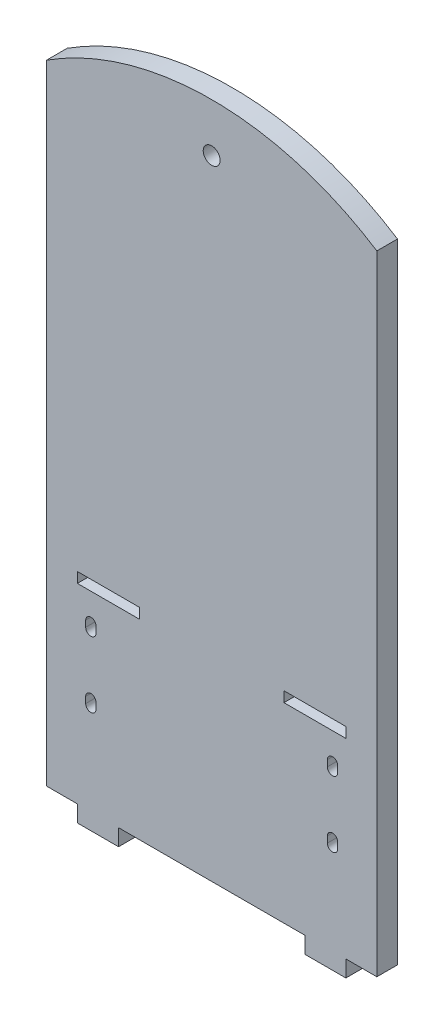
SolidWorks part; units mm, degrees
ref_plane "前基準面" through (0, 0, 0) normal (0, 0, 1) x (1, 0, 0)
ref_plane "上基準面" through (0, 0, 0) normal (0, 1, 0) x (1, 0, 0)
ref_plane "右基準面" through (0, 0, 0) normal (1, 0, 0) x (0, 0, -1)
sketch "草圖1" plane through (0, 0, 0) normal (0, 0, 1) x (1, 0, 0)
  line L0 (-80, 0) -> (-65, 0)
  line L1 (-80, 0) -> (-80, 304.5)
  line L2 (80, 0) -> (80, 304.5)
  line L3 (0, 299.9843) -> (0, -20.7711) construction
  line L5 (-65, 0) -> (-65, -8)
  line L6 (-65, -8) -> (-45.1, -8)
  line L7 (-45.1, 0) -> (-45.1, -8)
  line L12 (65, -8) -> (45.1, -8)
  line L13 (45.1, 0) -> (45.1, -8)
  line L15 (65, 0) -> (65, -8)
  line L16 (-45.1, 0) -> (45.1, 0)
  line L17 (65, 0) -> (80, 0)
  line L18 (-21.8, 304.5) -> (-15, 33.5) construction
  line L19 (28.5, 5) -> (-28.5, 5) construction
  line L20 (28.5, 5) -> (28.5, 62) construction
  line L21 (28.5, 62) -> (-28.5, 62) construction
  line L22 (-28.5, 5) -> (-28.5, 62) construction
  line L23 (21.8, 304.5) -> (15, 33.5) construction
  line L24 (-58.525, 76.1) -> (-58.525, 79.1) construction
  line L25 (-61.025, 76.1) -> (-61.025, 79.1)
  line L26 (-56.025, 76.1) -> (-56.025, 79.1)
  line L27 (-58.525, 44.1) -> (-58.525, 47.1) construction
  line L28 (-61.025, 44.1) -> (-61.025, 47.1)
  line L29 (-56.025, 44.1) -> (-56.025, 47.1)
  line L30 (-67.625, 89.2) -> (-67.625, 34) construction
  line L31 (-67.625, 89.2) -> (-49.425, 89.2) construction
  line L32 (-49.425, 89.2) -> (-49.425, 34) construction
  line L33 (-67.625, 34) -> (-49.425, 34) construction
  line L34 (-49.425, 61.6) -> (-67.625, 61.6) construction
  line L35 (-58.525, 89.2) -> (-58.525, 34) construction
  line L36 (58.525, 44.1) -> (58.525, 47.1) construction
  line L37 (61.025, 44.1) -> (61.025, 47.1)
  line L38 (56.025, 44.1) -> (56.025, 47.1)
  line L39 (58.525, 76.1) -> (58.525, 79.1) construction
  line L40 (61.025, 76.1) -> (61.025, 79.1)
  line L41 (56.025, 76.1) -> (56.025, 79.1)
  line L42 (76.4706, 328) -> (-76.4706, 328) construction
  arc A0 (-80, 304.5) -> (80, 304.5) centre (0, 304.5) cw construction
  circle A1 centre (0, 304.5) radius 4.1
  circle A2 centre (0, 33.5) radius 4 construction
  circle A3 centre (0, 33.5) radius 15 construction
  circle A4 centre (0, 304.5) radius 21.8 construction
  arc A5 (-61.025, 76.1) -> (-56.025, 76.1) centre (-58.525, 76.1) ccw
  arc A6 (-56.025, 79.1) -> (-61.025, 79.1) centre (-58.525, 79.1) ccw
  arc A7 (-61.025, 44.1) -> (-56.025, 44.1) centre (-58.525, 44.1) ccw
  arc A8 (-56.025, 47.1) -> (-61.025, 47.1) centre (-58.525, 47.1) ccw
  arc A9 (61.025, 44.1) -> (56.025, 44.1) centre (58.525, 44.1) cw
  arc A10 (56.025, 47.1) -> (61.025, 47.1) centre (58.525, 47.1) cw
  arc A11 (61.025, 76.1) -> (56.025, 76.1) centre (58.525, 76.1) cw
  arc A12 (56.025, 79.1) -> (61.025, 79.1) centre (58.525, 79.1) cw
  arc A13 (-80, 304.5) -> (80, 304.5) centre (0, 180.0798) cw
  point P17 (0, 62)
  point P25 (-28.5, 33.5)
  point P31 (-58.525, 77.6)
  point P39 (-58.525, 45.6)
  point P45 (-58.525, 49.6)
  point P46 (-58.525, 73.6)
  point P47 (-58.525, 41.6)
  point P48 (-58.525, 81.6)
  point P49 (-58.525, 61.6)
  point P63 (58.525, 45.6)
  point P70 (58.525, 77.6)
  point P75 (-80, 304.5)
  point P76 (0, 0)
  point P77 (0, 0)
  point P78 (0, 384.5)
  point P79 (0, 0)
  point P80 (-80, 304.5)
  dimension "D2" = 8.2
  dimension "D8" = 8
  dimension "D9" = 43.6
  dimension "D11" = 30
  dimension "D22" = 328
  dimension "D1" = 160
  dimension "D3" = 8
  dimension "D4" = 19.9
  dimension "D5" = 15
  dimension "D6" = 57
  dimension "D7" = 57
  dimension "D10" = 271
  dimension "D12" = 24
  dimension "D13" = 40
  dimension "D14" = 5
  dimension "D15" = 7.6
  dimension "D16" = 18.2
  dimension "D17" = 34
  dimension "D18" = 5.25
  dimension "D19" = 392.5
  dimension "D20" = 5
  dimension "D21" = 55.2
extrude "填料-伸長1" add sketch "草圖1" against normal blind 10
sketch "草圖2" plane through (0, 0, 0) normal (0, 0, 1) x (1, 0, 0)
  line L0 (20.9897, 303.8413) -> (12.4938, 33.1079) construction
  line L1 (-20.9897, 303.8413) -> (-12.4938, 33.1079) construction
  line L2 (85.3199, 95) -> (-141.7674, 95) construction
  line L3 (28.5, 62) -> (-28.5, 62) construction
  line L4 (28.5, 62) -> (28.5, 5) construction
  line L5 (28.5, 5) -> (-28.5, 5) construction
  line L6 (-28.5, 62) -> (-28.5, 5) construction
  line L7 (0, 5) -> (0, 62) construction
  line L8 (28.5, 33.5) -> (-28.5, 33.5) construction
  line L9 (-45.1, 0) -> (45.1, 0) construction
  line L10 (0, 0) -> (0, 407.6307) construction
  line L11 (-107.05, 139.5) -> (7, 139.5) construction
  line L12 (35, 97.5) -> (65.05, 97.5)
  line L13 (35, 97.5) -> (35, 92.5)
  line L14 (35, 92.5) -> (65.05, 92.5)
  line L15 (65.05, 97.5) -> (65.05, 92.5)
  line L16 (50.025, 92.5) -> (50.025, 97.5) construction
  line L17 (35, 95) -> (65.05, 95) construction
  line L18 (-65.05, 97.5) -> (-35, 97.5)
  line L19 (-65.05, 97.5) -> (-65.05, 92.5)
  line L20 (-65.05, 92.5) -> (-35, 92.5)
  line L21 (-35, 97.5) -> (-35, 92.5)
  line L22 (-50.025, 92.5) -> (-50.025, 97.5) construction
  line L23 (-65.05, 95) -> (-35, 95) construction
  line L27 (-107.05, 139.5) -> (-107.05, 50.5) construction
  line L28 (-107.05, 50.5) -> (7, 50.5) construction
  line L29 (7, 139.5) -> (7, 50.5) construction
  circle A0 centre (0, 304.5) radius 4.1 construction
  circle A1 centre (0, 304.5) radius 4.1 construction
  circle A2 centre (0, 33.5) radius 4 construction
  circle A3 centre (0, 33.5) radius 4 construction
  circle A4 centre (0, 304.5) radius 21 construction
  circle A5 centre (0, 33.5) radius 12.5 construction
  point P24 (50.025, 95)
  point P28 (-50.025, 95)
  point P35 (14.4361, 95)
  point P37 (-14.4361, 95)
  dimension "D1" = 25
  dimension "D2" = 42
  dimension "D3" = 57
  dimension "D4" = 57
  dimension "D5" = 95
  dimension "D6" = 5
  dimension "D7" = 30.05
  dimension "D8" = 70
  dimension "D9" = 28.8721
  dimension "D10" = 42
  dimension "D11" = 165
extrude "除料-伸長1" cut sketch "草圖2" against normal through all
